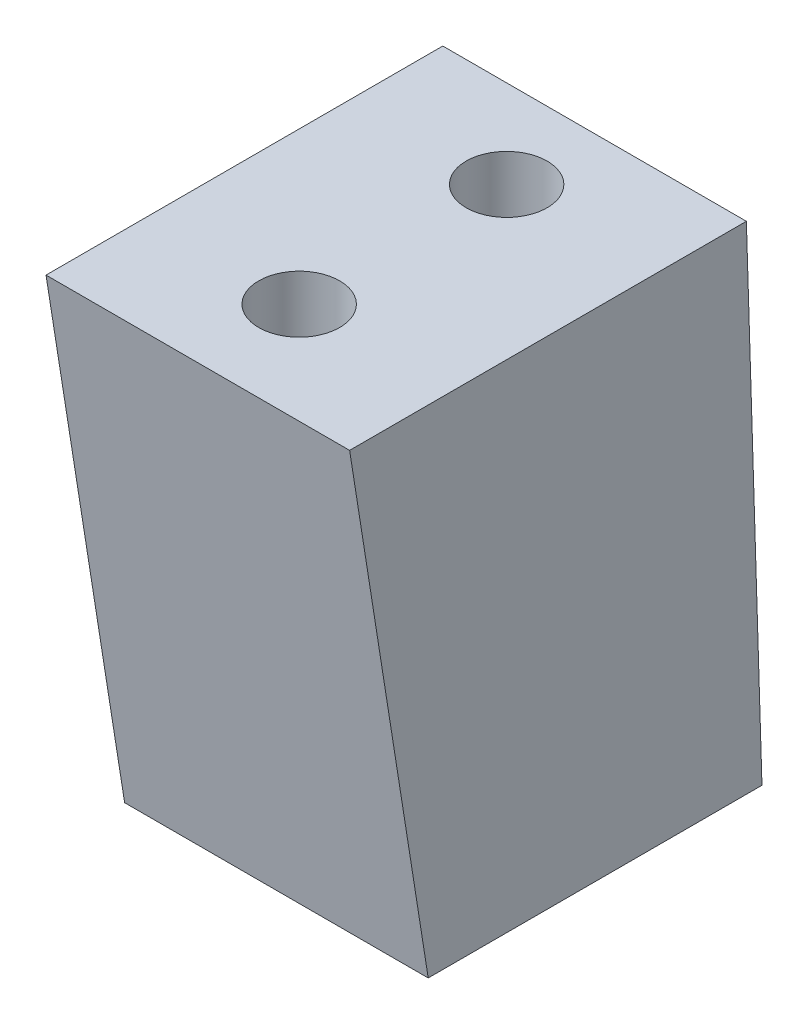
SolidWorks part; units mm, degrees
ref_plane "Plan de face" through (0, 0, 0) normal (0, 0, 1) x (1, 0, 0)
ref_plane "Plan de dessus" through (0, 0, 0) normal (0, 1, 0) x (1, 0, 0)
ref_plane "Plan de droite" through (0, 0, 0) normal (1, 0, 0) x (0, 0, -1)
sketch "Esquisse1" plane through (0, 0, 0) normal (0, 0, 1) x (1, 0, 0)
  line L1 (0, 0) -> (-15, 0)
  line L2 (0, 0) -> (0, 24.52)
  line L3 (0, 24.52) -> (-15, 24.52)
  line L4 (-15, 0) -> (-15, 24.52)
  dimension "D1" = 15
  dimension "D2" = 24.52
extrude "Boss.-Extru.1" add sketch "Esquisse1" against normal blind 20.5
sketch "Esquisse3" plane through (0, 0, 0) normal (0, -1, 0) x (1, 0, 0)
  line L0 (0, -10.25) -> (-15, -10.25)
  line L1 (0, -20.5) -> (0, 0) construction
  line L2 (-15, -20.5) -> (-15, 0) construction
  line L3 (-7.5, -10.25) -> (-7.5, -20.5)
  line L4 (-15, -20.5) -> (0, -20.5) construction
  line L5 (-7.5, -10.25) -> (-7.5, 0)
  line L6 (-15, 0) -> (0, 0) construction
  line L7 (-7.5, -10.25) -> (-7.5, -15.375)
  line L8 (-7.5, -10.25) -> (-7.5, -5.125)
  circle A3 centre (-7.5, -15.375) radius 2
  circle A4 centre (-7.5, -7.6875) radius 2
extrude "Enlèv. mat.-Extru.2" cut sketch "Esquisse3" against normal blind 3 contours L7 A3 L3 | L3 A3 L7 | L8 A4 | L8 A4 region at (-6.6512, 0, -15.375) region at (-8.3488, 0, -15.375) region at (-8.3488, 0, -7.6875) region at (-6.6512, 0, -7.6875)
sketch "Esquisse2" plane through (0, 24.52, 0) normal (0, 1, 0) x (1, 0, 0)
  line L0 (-15, 10.25) -> (0, 10.25)
  line L1 (-15, 20.5) -> (-15, 0) construction
  line L2 (0, 20.5) -> (0, 0) construction
  line L3 (-7.5, 10.25) -> (-7.5, 20.5)
  line L4 (0, 20.5) -> (-15, 20.5) construction
  line L5 (-7.5, 10.25) -> (-7.5, 0)
  line L6 (0, 0) -> (-15, 0) construction
  circle A0 centre (-7.5, 15.375) radius 2
  circle A1 centre (-7.5, 5.125) radius 2
  point P17 (0, 0)
extrude "Enlèv. mat.-Extru.1" cut sketch "Esquisse2" against normal blind 3 contours L3 A0 | L3 A0 | L5 A1 | L5 A1 region at (-8.3488, 24.52, -15.375) region at (-6.6512, 24.52, -15.375) region at (-6.6512, 24.52, -5.125) region at (-8.3488, 24.52, -5.125)
chamfer "Chanfrein2" distance 4 angle 81 1 edges at (-7.5, 0, 0) first distance on face at (-7.5, 0, -17.375)
chamfer "Chanfrein3" distance 0.78 angle 88.2 1 edges at (-7.5, 24.52, -20.5) first distance on face at (-9.5, 24.52, -15.375)
